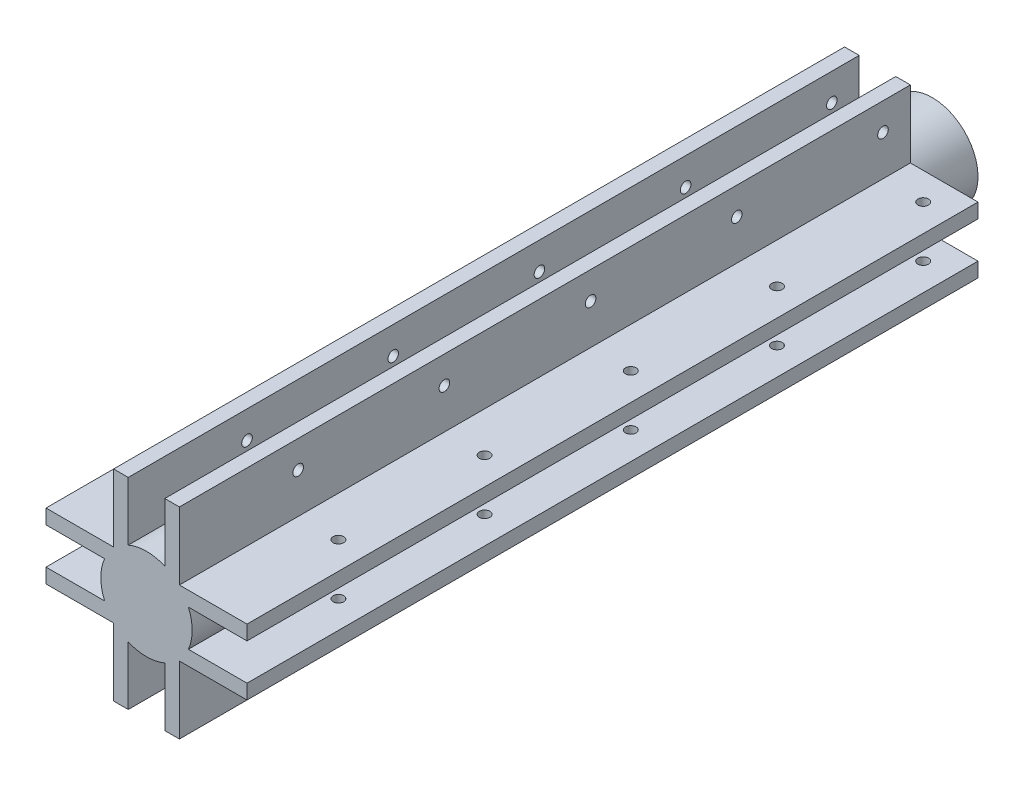
SolidWorks part; units mm, degrees
ref_plane "Front Plane" through (0, 0, 0) normal (0, 0, 1) x (1, 0, 0)
ref_plane "Top Plane" through (0, 0, 0) normal (0, 1, 0) x (1, 0, 0)
ref_plane "Right Plane" through (0, 0, 0) normal (1, 0, 0) x (0, 0, -1)
sketch "Sketch1" plane through (0, 0, 0) normal (0, 0, 1) x (1, 0, 0)
  circle A0 centre (0, 0) radius 12.5
  dimension "D2" = 25
extrude "Boss-Extrude1" add sketch "Sketch1" along normal mid plane 200
sketch "Sketch4" plane through (0, 0, 100) normal (0, 0, 1) x (1, 0, 0)
  line L0 (30.25, 0) -> (-30.25, 0) construction
  line L2 (-9, 0) -> (-5, 0)
  line L3 (0, 0) -> (0, 15.8331) construction
  line L4 (-9, 0) -> (-9, 27.5)
  line L5 (-9, 27.5) -> (-5, 27.5)
  line L6 (-5, 0) -> (-5, 27.5)
  line L7 (0, -30.25) -> (0, 30.25) construction
  line L8 (9, 27.5) -> (5, 27.5)
  line L9 (5, 0) -> (5, 27.5)
  line L10 (9, 0) -> (5, 0)
  line L11 (9, 0) -> (9, 27.5)
  dimension "D1" = 27.5
  dimension "D3" = 5
  dimension "D2" = 4
extrude "Boss-Extrude3" add sketch "Sketch4" against normal up to surface (200 mm away) up to face at (12.5, 0, -100)
pattern_circular "CirPattern7" count 4 over 360 about axis through (0, 0, -100) along (0, 0, 1) of "Boss-Extrude3"
sketch "Sketch7" plane through (-9, 0, 0) normal (-1, 0, 0) x (0, 0, 1)
  line L0 (-100, 27.5) -> (100, 27.5) construction
  line L1 (-100, 9) -> (-100, 27.5) construction
  circle A0 centre (-92.5, 20) radius 1.45
  circle A1 centre (-52.5, 20) radius 1.45
  circle A2 centre (-12.5, 20) radius 1.45
  circle A3 centre (27.5, 20) radius 1.45
  circle A4 centre (67.5, 20) radius 1.45
  dimension "D1" = 2.9
  dimension "D2" = 7.5
  dimension "D3" = 7.5
  dimension "D4" = 5
extrude "Cut-Extrude2" cut sketch "Sketch7" against normal blind 27
pattern_circular "CirPattern9" count 4 over 360 about axis through (0, 0, 100) along (0, 0, 1) of "Cut-Extrude2"
sketch "Sketch10" plane through (0, 0, -100) normal (0, 0, -1) x (-1, 0, 0)
  circle A0 centre (0, 0) radius 12.5
  dimension "D1" = 25
extrude "Boss-Extrude4" add sketch "Sketch10" along normal blind 15
equation "\"drumDiameter\"= 25"
equation "\"D2@Sketch1\"=\"drumDiameter\""
equation "\"drumLength\"= 200"
equation "\"D1@Sketch4\"=\"drumDiameter\"*(0.5+\"drumAbove\")"
equation "\"foamThickness\"= 10"
equation "\"D3@Sketch4\"=\"foamThickness\"/2"
equation "\"drumAbove\"= 0.6"
equation "\"D2@Sketch7\"=\"drumDiameter\"*\"drumAbove\"/2"
equation "\"holderThicc\"= 4"
equation "\"D2@Sketch4\"=\"holderThicc\""
equation "\"D1@Boss-Extrude1\"=\"drumLength\""
equation "\"squareBarLength\" = 12.5"
equation "\"D1@Sketch8\"=\"squareBarLength\""
equation "\"D2@Sketch9\"=(\"drumDiameter\"/2-\"squareBarLength\"/2)/2"
equation "\"D1@Sketch10\"=\"drumDiameter\""
equation "\"squareBarShortLen\"=12.3"
equation "\"D2@Sketch8\"=\"squareBarShortLen\""
